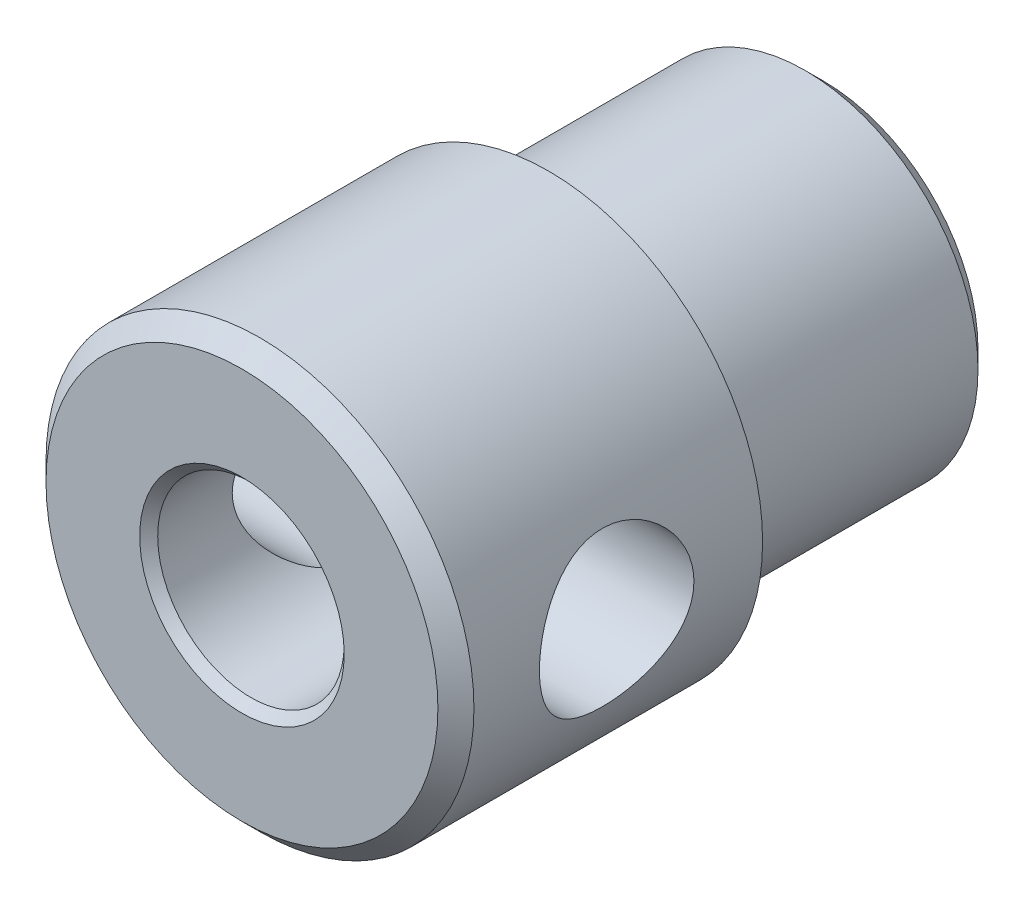
SolidWorks part; units mm, degrees
material "Chrome Stainless Steel"
ref_plane "Front Plane" through (0, 0, 0) normal (0, 0, 1) x (1, 0, 0)
ref_plane "Top Plane" through (0, 0, 0) normal (0, 1, 0) x (1, 0, 0)
ref_plane "Right Plane" through (0, 0, 0) normal (1, 0, 0) x (0, 0, -1)
sketch "Sketch1" plane through (0, 0, 0) normal (0, 0, 1) x (1, 0, 0)
  circle A0 centre (0, 0) radius 4.7498
  circle A1 centre (0, 0) radius 2.0701
  dimension "D1" = 9.4996
  dimension "D2" = 4.1402
extrude "Extrude1" add sketch "Sketch1" along normal blind 6.8072
sketch "Sketch2" plane through (0, 0, 0) normal (0, 0, -1) x (-1, 0, 0)
  circle A0 centre (0, 0) radius 2.0701
  circle A1 centre (0, 0) radius 3.8354
  circle A2 centre (0, 0) radius 2.0701 construction
  dimension "D1" = 7.6708
extrude "Extrude2" add sketch "Sketch2" along normal blind 6.096
chamfer "Chamfer2" distance 0.2 angle 45 1 edges at (-2.0701, 0, -6.096)
chamfer "Chamfer3" distance 0.4 angle 45 1 edges at (-3.8354, 0, -6.096)
chamfer "Chamfer4" distance 0.4 angle 45 1 edges at (4.7498, 0, 6.8072)
chamfer "Chamfer5" distance 0.2 angle 45 1 edges at (2.0701, 0, 6.8072)
sketch "Sketch3" plane through (0, 0, 6.8072) normal (0, 0, 1) x (1, 0, 0)
  circle A0 centre (0, 0) radius 4.3498 construction
  point P0 (-4.3498, 0)
ref_plane "Plane1" through (-4.7498, 0, 6.4072) normal (-1, 0, 0) x (0, 0, 1)
sketch "Sketch4" plane through (-4.7498, 0, 6.4072) normal (-1, 0, 0) x (0, 0, 1)
  line L0 (-6.4072, 0) -> (-3.1687, 0) construction
  circle A0 centre (-3.1687, 0) radius 1.7145
  dimension "D1" = 3.429
  dimension "D2" = 3.2385
extrude "Cut-Extrude1" cut sketch "Sketch4" against normal through all
